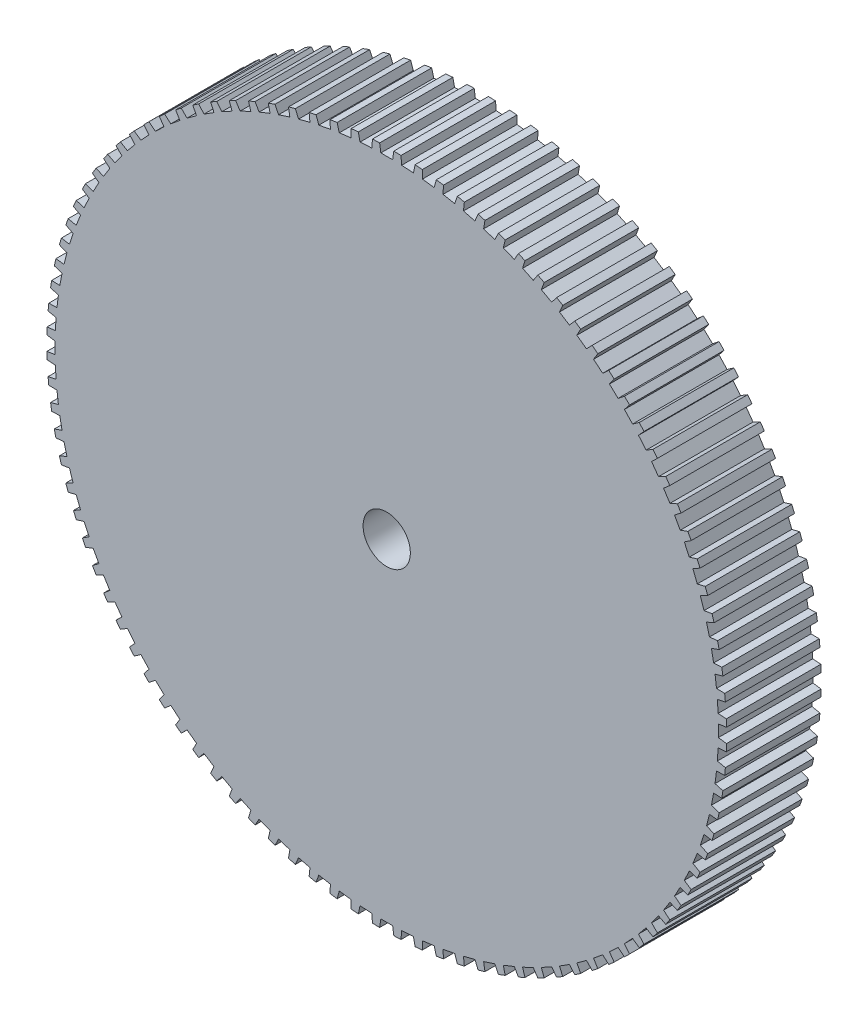
SolidWorks part; units mm, degrees
ref_plane "Front Plane" through (0, 0, 0) normal (0, 0, 1) x (1, 0, 0)
ref_plane "Top Plane" through (0, 0, 0) normal (0, 1, 0) x (1, 0, 0)
ref_plane "Right Plane" through (0, 0, 0) normal (1, 0, 0) x (0, 0, -1)
sketch "Sketch1" plane through (0, 0, 0) normal (0, 0, 1) x (1, 0, 0)
  circle A0 centre (0, 0) radius 31.75 construction
  circle A2 centre (0, 0) radius 28.75
  dimension "D1" = 63.5
  dimension "rubberthk" = 3
extrude "Boss-Extrude1" add sketch "Sketch1" along normal blind 8
sketch "Sketch4" plane through (0, 0, 0) normal (0, 0, -1) x (-1, 0, 0)
  circle A0 centre (0, 0) radius 4.85
  dimension "D1" = 9.7
extrude "Boss-Extrude2" add sketch "Sketch4" along normal blind 8
sketch "Sketch2" plane through (0, 0, 8) normal (0, 0, 1) x (1, 0, 0)
  circle A0 centre (0, 0) radius 4
  dimension "D1" = 8
extrude "Cut-Extrude1" cut sketch "Sketch2" against normal blind 4.35
sketch "Sketch5" plane through (0, 0, 3.65) normal (0, 0, 1) x (1, 0, 0)
  circle A0 centre (0, 0) radius 2
  dimension "D1" = 4
extrude "Cut-Extrude2" cut sketch "Sketch5" against normal offset from surface (4.15 mm away) 7.5 up to face at (-4.85, 0, -8)
sketch "Sketch6" plane through (0, 0, -8) normal (0, 0, -1) x (-1, 0, 0)
  line L0 (2.0785, 1.95) -> (-2.0785, 1.95)
  line L1 (-2.0785, -1.95) -> (2.0785, -1.95)
  arc A0 (2.0785, -1.95) -> (2.0785, 1.95) centre (0, 0) ccw
  arc A1 (-2.0785, 1.95) -> (-2.0785, -1.95) centre (0, 0) ccw
  dimension "D2" = 5.7
  dimension "D1" = 3.9
extrude "Cut-Extrude3" cut sketch "Sketch6" against normal up to surface (7.5 mm away) up to face at (-2, 0, -0.5)
sketch "Sketch7" plane through (0, 0, 8) normal (0, 0, 1) x (1, 0, 0)
  line L0 (-0.6, 28.7437) -> (-0.5, 28.06)
  line L1 (-0.5, 28.06) -> (0.5, 28.06)
  line L2 (0.5, 28.06) -> (0.6, 28.7437)
  line L3 (0, 0) -> (-0.6, 28.7437) construction
  line L4 (0, 0) -> (0.6, 28.7437) construction
  circle A0 centre (0, 0) radius 28.75 construction
  arc A1 (0.6, 28.7437) -> (-0.6, 28.7437) centre (0, 0) ccw
  point P8 (0, 28.06)
  dimension "D1" = 1
  dimension "D2" = 1.2
  dimension "D3" = 0.69
extrude "Cut-Extrude4" cut sketch "Sketch7" against normal through all
pattern_circular "CirPattern1" count 100 over 360 about axis through (0, 0, 8) along (0, 0, -1) of "Cut-Extrude4"
sketch "Sketch8" plane through (0, 0, 3.65) normal (0, 0, 1) x (1, 0, 0)
  circle A0 centre (0, 0) radius 2 construction
  circle A1 centre (0, 0) radius 4
  circle A2 centre (0, 0) radius 4
  circle A3 centre (0, 0) radius 2
  dimension "D1" = 0
extrude "ReverseCountersink" add sketch "Sketch8" along normal up to surface (4.35 mm away) up to face at (0, 0, 8)
equation "\"width\"= 24"
equation "\"thk\"= 3"
equation "\"holesize\"= 4.2"
equation "\"holedistance\"= ( 20 + 12 ) / 2"
equation "\"threaded_hole\"= 3.9"
equation "\"fillet_radius\"= 2"
equation "\"ground_clearance\"= 25"
equation "\"tire_thk\"= 3"
equation "\"innerwheel_diam\" = \"wheel_diam\"-2*\"tire_thk\""
equation "\"innerwheel_thk\"= 8"
equation "\"wheel_diam\"= 2*(\"width\"/2+\"ground_clearance\")"
equation "\"rubberthk@Sketch1\"=\"tire_thk\""
equation "\"D1@Boss-Extrude1\"=\"innerwheel_thk\""
equation "\"coloursensor_holesize\"= 2.65"
equation "\"hole_to_edge\" = 4"
equation "\"D1@Sketch1\"=57.5 + 2 * \"tire_thk\""
